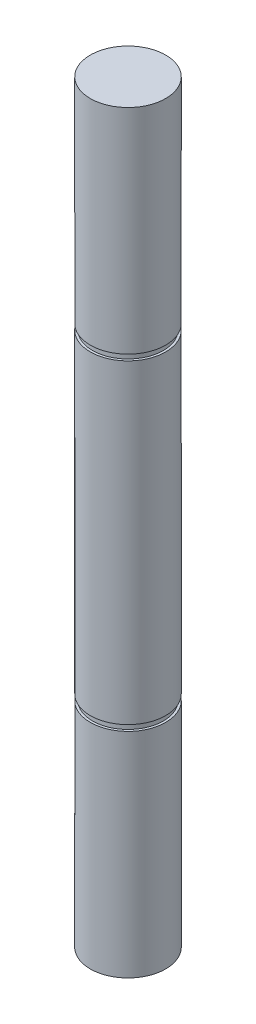
SolidWorks part; units mm, degrees
ref_plane "Front Plane" through (0, 0, 0) normal (0, 0, 1) x (1, 0, 0)
ref_plane "Top Plane" through (0, 0, 0) normal (0, 1, 0) x (1, 0, 0)
ref_plane "Right Plane" through (0, 0, 0) normal (1, 0, 0) x (0, 0, -1)
sketch "Sketch1" plane through (0, 0, 0) normal (0, 1, 0) x (1, 0, 0)
  circle A0 centre (0, 0) radius 4.7625
  dimension "D1" = 9.525
extrude "Boss-Extrude1" add sketch "Sketch1" against normal blind 95.25
sketch3d "3DSketch2"
  circle A0 centre (0, -68.2625, 0) radius 5.08
  circle A1 centre (0, -95.25, 0) radius 4.7625 construction
  point P2 (0, -73.3425, 0)
  point P6 (0, -90.4875, 0)
  dimension "D2" = 10.16
  dimension "D1" = 26.9875
extrude "Cut-Extrude2" cut sketch "3DSketch2" along direction (0, 1, 0) on the side of the normal blind 0.7366
sketch "Sketch7" plane through (0, -68.2625, 0) normal (0, 1, 0) x (1, 0, 0)
  circle A0 centre (0, 0) radius 4.4704
  dimension "D1" = 8.9408
extrude "Boss-Extrude2" add sketch "Sketch7" along normal up to surface (0.7366 mm away) contours A0 up to face at (-4.7625, -67.5259, 0)
sketch3d "3DSketch3"
  circle A0 centre (0, -26.9875, 0) radius 12.7
  circle A1 centre (0, 0, 0) radius 4.7625 construction
  point P2 (0, -14.2875, 0)
  point P8 (0, 4.7625, 0)
  dimension "D2" = 25.4
  dimension "D1" = 26.9875
extrude "Cut-Extrude3" cut sketch "3DSketch3" along direction (0, 1, 0) on the side against the normal blind 0.7366
sketch "Sketch8" plane through (0, -27.7241, 0) normal (0, 1, 0) x (1, 0, 0)
  circle A0 centre (0, 0) radius 4.4704
  dimension "D1" = 8.9408
extrude "Boss-Extrude3" add sketch "Sketch8" along normal up to surface (0.7366 mm away) up to face at (0, -26.9875, -4.7625)
